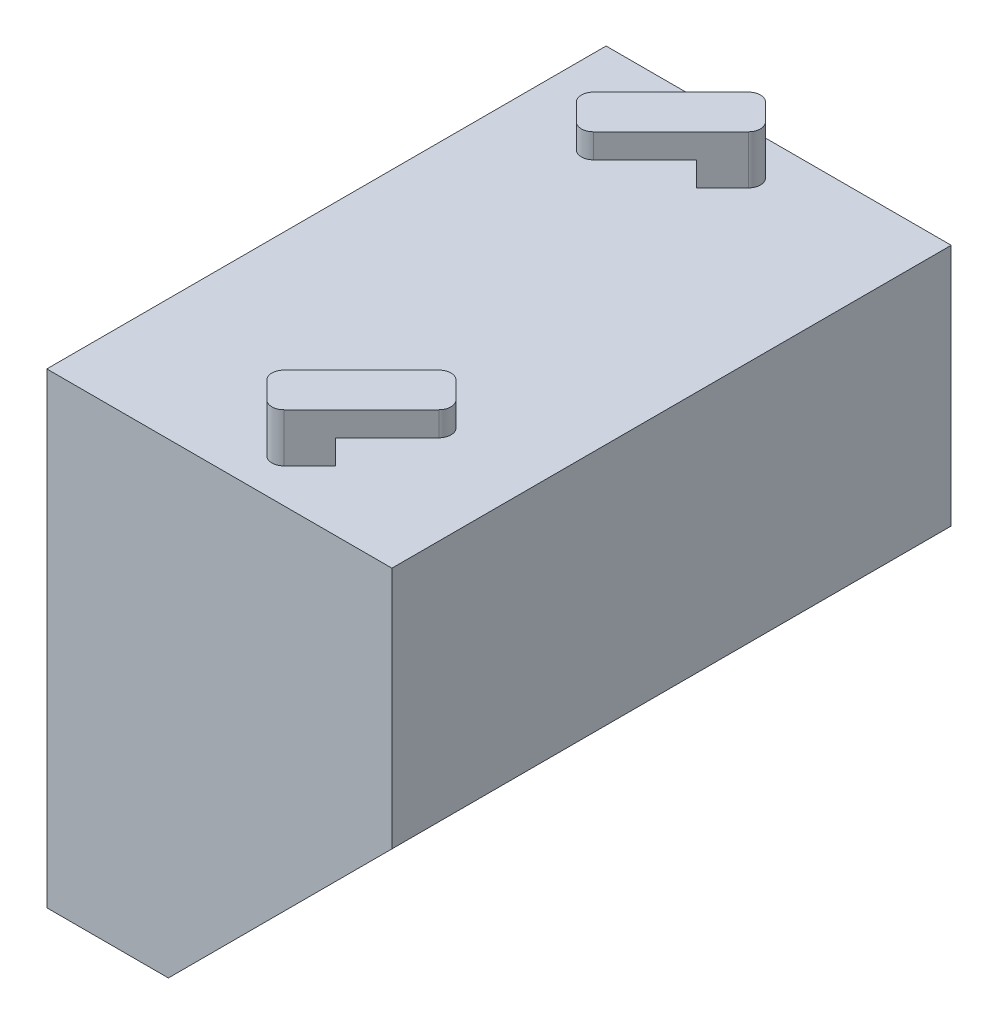
SolidWorks part; units mm, degrees
ref_plane "Plan de face" through (0, 0, 0) normal (0, 0, 1) x (1, 0, 0)
ref_plane "Plan de dessus" through (0, 0, 0) normal (0, 1, 0) x (1, 0, 0)
ref_plane "Plan de droite" through (0, 0, 0) normal (1, 0, 0) x (0, 0, -1)
sketch "Esquisse1" plane through (0, 0, 0) normal (0, 0, 1) x (1, 0, 0)
  line L0 (0, 38.3848) -> (28.3848, 38.3848)
  line L1 (28.3848, 38.3848) -> (28.3848, 18.3848)
  line L2 (28.3848, 18.3848) -> (10, 0)
  line L3 (10, 0) -> (0, 0)
  line L4 (0, 37.3848) -> (27.3848, 37.3848)
  line L5 (27.3848, 37.3848) -> (27.3848, 18.799)
  line L6 (27.3848, 18.799) -> (9.5858, 1)
  line L7 (9.5858, 1) -> (0, 1)
  line L8 (0, 37.3848) -> (0, 38.3848)
  line L9 (0, 1) -> (0, 0)
  dimension "D1" = 135
  dimension "D2" = 26
  dimension "D3" = 10
  dimension "D4" = 20
extrude "Boss.-Extru.1" add sketch "Esquisse1" along normal blind 22 and the other way blind 22
sketch "Esquisse2" plane through (0, 0, 0) normal (0, 0, 1) x (1, 0, 0)
  line L0 (0, 38.3848) -> (0, 0)
  line L1 (0, 0) -> (10, 0)
  line L2 (10, 0) -> (28.3848, 18.3848)
  line L3 (28.3848, 18.3848) -> (28.3848, 38.3848)
  line L4 (28.3848, 38.3848) -> (0, 38.3848)
extrude "Boss.-Extru.5" add sketch "Esquisse2" along normal blind 1 from offset 22 contours L3 L4 L0 L1 L2 region at (12.7119, 21.5908, 0)
sketch "Esquisse3" plane through (0, 0, 0) normal (0, 0, 1) x (1, 0, 0)
  line L0 (0, 38.3848) -> (0, 0)
  line L1 (0, 0) -> (10, 0)
  line L2 (10, 0) -> (28.3848, 18.3848)
  line L3 (28.3848, 18.3848) -> (28.3848, 38.3848)
  line L4 (28.3848, 38.3848) -> (0, 38.3848)
extrude "Boss.-Extru.6" add sketch "Esquisse3" against normal blind 1 from offset 22 offset against normal yes
sketch "Esquisse4" plane through (0, 38.3848, 0) normal (0, 1, 0) x (1, 0, 0)
  line L0 (-10.5542, 0) -> (42.7606, 0) construction
  line L1 (14.1924, 24.6213) -> (14.1924, -26.0622) construction
  line L2 (0, 23) -> (0, -23) construction
  line L3 (28.3848, 23) -> (28.3848, -23) construction
  line L4 (-3.7969, 17.9893) -> (31.9754, -17.783) construction
  line L5 (11.0104, 19.4454) -> (13.8388, 16.617)
  line L6 (13.8388, 16.617) -> (16.6673, 19.4454)
  line L7 (16.6673, 19.4454) -> (13.8388, 22.2739)
  line L8 (13.8388, 22.2739) -> (11.0104, 19.4454)
  line L9 (15.9602, -20.8597) -> (18.7886, -18.0312)
  line L10 (18.7886, -18.0312) -> (15.9602, -15.2028)
  line L11 (15.9602, -15.2028) -> (13.1317, -18.0312)
  line L12 (13.1317, -18.0312) -> (15.9602, -20.8597)
  point P9 (14.1924, 0)
  point P23 (14.8995, 0.7071)
  dimension "D1" = 45
  dimension "D2" = 4
  dimension "D3" = 4
  dimension "D4" = 11.5
  dimension "D5" = 12
  dimension "D6" = 2
extrude "Boss.-Extru.7" add sketch "Esquisse4" along normal blind 2
sketch "Esquisse5" plane through (0, 40.3848, 0) normal (0, 1, 0) x (1, 0, 0)
  line L0 (13.8388, 22.2739) -> (16.6673, 19.4454)
  line L1 (16.6673, 19.4454) -> (8.8891, 11.6673)
  line L2 (8.8891, 11.6673) -> (6.0607, 14.4957)
  line L3 (6.0607, 14.4957) -> (13.8388, 22.2739)
  line L4 (13.1317, -18.0312) -> (15.9602, -20.8597)
  line L5 (15.9602, -20.8597) -> (23.7383, -13.0815)
  line L6 (23.7383, -13.0815) -> (20.9099, -10.253)
  line L7 (20.9099, -10.253) -> (13.1317, -18.0312)
  dimension "D1" = 11
  dimension "11" = 11
extrude "Boss.-Extru.8" add sketch "Esquisse5" along normal blind 2
fillet "Congé1" radius 1 8 edges at (20.9099, 41.3848, 10.253) (23.7383, 41.3848, 13.0815) (6.0607, 41.3848, -14.4957) (8.8891, 41.3848, -11.6673) (13.8388, 40.3848, -22.2739) (16.6673, 40.3848, -19.4454) (13.1317, 40.3848, 18.0312) (15.9602, 40.3848, 20.8597)
sketch "Esquisse6" plane through (5, -5, 0) normal (0.7071, -0.7071, 0) x (0, 0, -1)
  line L0 (30.9815, 20.0711) -> (-29.0548, 20.0711) construction
  line L1 (11.75, 31.8211) -> (-11.75, 31.8211)
  line L2 (11.75, 31.8211) -> (11.75, 8.3211)
  line L3 (11.75, 8.3211) -> (-11.75, 8.3211)
  line L4 (-11.75, 31.8211) -> (-11.75, 8.3211)
  line L5 (23, 33.0711) -> (-23, 33.0711) construction
  line L6 (23, 7.0711) -> (-23, 7.0711) construction
  line L7 (0, 54.7353) -> (0, -12.4113) construction
  line L8 (-23, 7.0711) -> (-23, 33.0711) construction
  line L9 (23, 7.0711) -> (23, 33.0711) construction
  circle A0 centre (14.25, 20.0711) radius 0.75
  circle A1 centre (-14.25, 20.0711) radius 0.75
  dimension "D3" = 1.5
  dimension "D4" = 1.5
  dimension "D1" = 23.5
  dimension "D2" = 23.5
  dimension "D5" = 14.25
extrude "Enlèv. mat.-Extru.1" cut sketch "Esquisse6" against normal up to next and the other way blind 2
